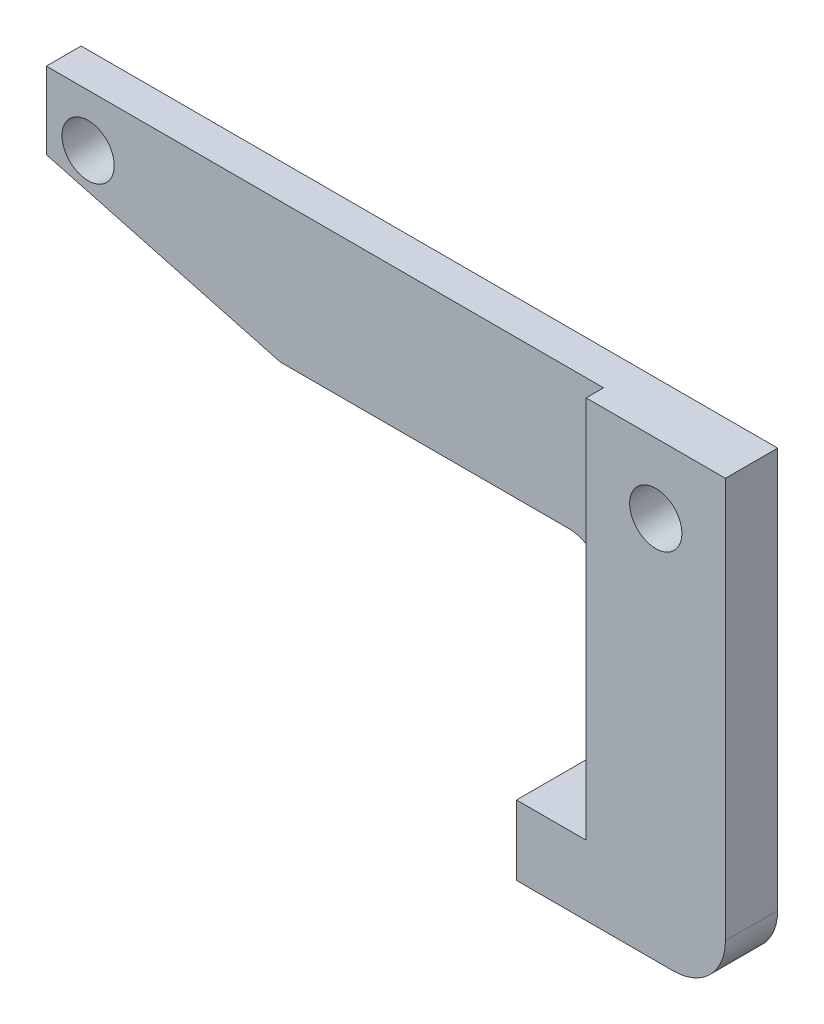
SolidWorks part; units mm, degrees
ref_plane "Front" through (0, 0, 0) normal (0, 0, 1) x (1, 0, 0)
ref_plane "Top" through (0, 0, 0) normal (0, 1, 0) x (1, 0, 0)
ref_plane "Right" through (0, 0, 0) normal (1, 0, 0) x (0, 0, -1)
sketch "Sketch1" plane through (0, 0, 0) normal (0, 0, 1) x (1, 0, 0)
  line L1 (-114.3, 12.7) -> (12.7, 12.7)
  line L2 (-114.3, 12.7) -> (-114.3, -12.7)
  line L3 (-114.3, -12.7) -> (-12.7, -12.7)
  line L4 (12.7, 12.7) -> (12.7, -69.85)
  line L6 (-12.7, -12.7) -> (-12.7, -57.15)
  line L9 (-12.7, -57.15) -> (-25.4, -57.15)
  line L11 (12.7, -69.85) -> (-25.4, -69.85)
  line L12 (-25.4, -57.15) -> (-25.4, -69.85)
  dimension "D1" = 25.4
  dimension "D2" = 127
  dimension "D3" = 44.45
  dimension "D4" = 82.55
  dimension "D5" = 12.7
  dimension "D6" = 12.7
  dimension "D7" = 38.1
  dimension "D8" = 25.4
extrude "Base-Extrude" add sketch "Sketch1" along normal blind 12.7
sketch "Sketch2" plane through (0, 0, 12.7) normal (0, 0, 1) x (1, 0, 0)
  circle A0 centre (0, 0) radius 4.7625
  dimension "D1" = 9.525
extrude "Cut-Extrude1" cut sketch "Sketch2" against normal through all
sketch "Sketch3" plane through (0, 0, 12.7) normal (0, 0, 1) x (1, 0, 0)
  line L1 (12.7, 12.7) -> (-114.3, 12.7) construction
  line L2 (-114.3, 12.7) -> (-114.3, -12.7) construction
  circle A0 centre (-106.68, 3.175) radius 4.7625
  dimension "D1" = 9.525
  dimension "D2" = 9.525
  dimension "D3" = 7.62
extrude "Cut-Extrude2" cut sketch "Sketch3" against normal through all
chamfer "Chamfer1" distance 11.43 angle 75 1 edges at (-114.3, -12.7, 6.35) first distance on face at (-114.3, 0, 6.35)
sketch "Sketch4" plane through (0, 0, 12.7) normal (0, 0, 1) x (1, 0, 0)
  line L1 (-12.7, -12.7) -> (-114.3, -12.7)
  line L2 (-12.7, -12.7) -> (-12.7, 12.7)
  line L3 (-12.7, 12.7) -> (-114.3, 12.7)
  line L4 (-114.3, -12.7) -> (-114.3, 12.7)
extrude "Cut-Extrude3" cut sketch "Sketch4" against normal blind 3.175
fillet "Fillet1" radius 9.525 1 edges at (12.7, -69.85, 6.35)
fillet "Fillet2" radius 6.35 1 edges at (-12.7, -12.7, 4.7625)
chamfer "Chamfer2" distance 3.175 angle 45 4 edges at (-11.1125, -69.85, 0) (9.9102, -67.0602, 0) (12.7, -23.8125, 0) (-50.8, 12.7, 0)
sketch "Sketch5" plane through (0, 0, 0) normal (0, 0, -1) x (-1, 0, 0)
  circle A0 centre (0, 0) radius 9.525
  dimension "D1" = 19.05
extrude "Cut-Extrude4" cut sketch "Sketch5" against normal blind 4.445
